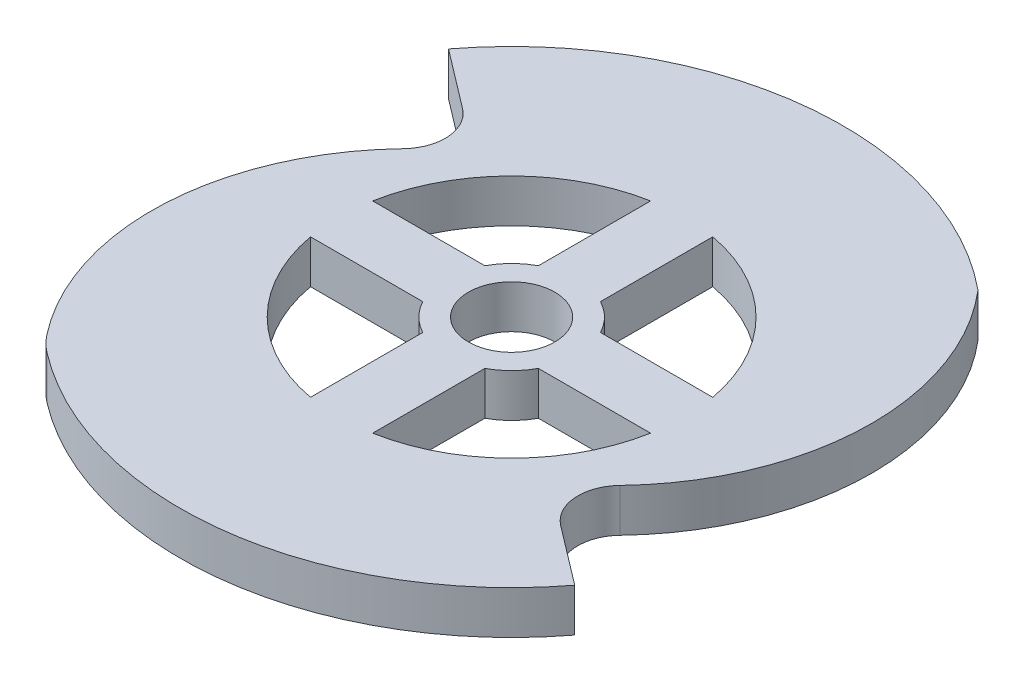
SolidWorks part; units mm, degrees
ref_plane "Front Plane" through (0, 0, 0) normal (0, 0, 1) x (1, 0, 0)
ref_plane "Top Plane" through (0, 0, 0) normal (0, 1, 0) x (1, 0, 0)
ref_plane "Right Plane" through (0, 0, 0) normal (1, 0, 0) x (0, 0, -1)
sketch "Sketch1" plane through (0, 0, 0) normal (0, 1, 0) x (1, 0, 0)
  line L0 (-61.0433, 46.4365) -> (-47.4391, 36.0875)
  line L5 (-61.0433, 46.4365) -> (61.0433, -46.4365) construction
  line L6 (-48.5581, -59.3696) -> (48.5581, 59.3696) construction
  line L7 (61.0433, -46.4365) -> (47.4391, -36.0875)
  line L17 (-7.1911, -13.1639) -> (-7.1911, -39.3483)
  line L26 (-7.1911, 39.3483) -> (-7.1911, 13.3811)
  line L28 (7.1911, 39.3483) -> (7.1911, 13.3811)
  line L29 (-7.1911, 39.3483) -> (7.1911, -39.3483) construction
  line L30 (-7.1911, -39.3483) -> (7.1911, 39.3483) construction
  line L31 (-39.3483, 7.1911) -> (-13.3811, 7.1911)
  line L33 (-39.3483, -7.1911) -> (-13.3811, -7.1911)
  line L35 (-39.3483, 7.1911) -> (39.3483, -7.1911) construction
  line L36 (-39.3483, -7.1911) -> (39.3483, 7.1911) construction
  line L38 (7.1911, -13.3811) -> (7.1911, -39.3483)
  line L39 (13.3811, 7.1911) -> (39.3483, 7.1911)
  line L42 (13.3811, -7.1911) -> (39.3483, -7.1911)
  arc A0 (-46.6235, -60.9006) -> (61.0433, -46.4365) centre (0, 0) ccw
  arc A1 (7.1911, -39.3483) -> (39.3483, -7.1911) centre (0, 0) ccw
  arc A2 (48.5581, 59.3696) -> (46.2784, -21.2046) centre (2.9877, 20.3396) cw
  arc A3 (-50.205, -57.3603) -> (-46.2784, 21.2046) centre (-2.9877, -20.3396) cw
  arc A4 (48.5581, 59.3696) -> (-61.0433, 46.4365) centre (0, 0) ccw
  arc A6 (-13.3811, -7.1911) -> (-7.1911, -13.3811) centre (0, 0) ccw
  arc A8 (13.3811, 7.1911) -> (7.1911, 13.3811) centre (0, 0) ccw
  arc A9 (-7.1911, 13.3811) -> (-13.3811, 7.1911) centre (0, 0) ccw
  arc A10 (-7.1911, 39.3483) -> (-39.3483, 7.1911) centre (0, 0) ccw
  arc A11 (39.3483, 7.1911) -> (7.1911, 39.3483) centre (0, 0) ccw
  arc A12 (-39.3483, -7.1911) -> (-7.1911, -39.3483) centre (0, 0) ccw
  circle A13 centre (0, 0) radius 10
  arc A14 (7.1911, -13.3811) -> (13.3811, -7.1911) centre (0, 0) ccw
  arc A15 (-46.6235, -60.9006) -> (-50.205, -57.3603) centre (-34.4659, -45.02) cw
  arc A16 (-47.4391, 36.0875) -> (-46.2784, 21.2046) centre (-53.4935, 28.1286) cw
  arc A17 (46.2784, -21.2046) -> (47.4391, -36.0875) centre (53.4935, -28.1286) ccw
  point P34 (37.6461, -28.6379)
  dimension "D1" = 20
  dimension "D2" = 10
  dimension "D3" = 10
extrude "Boss-Extrude4" add sketch "Sketch1" along normal blind 10 contours A2 A4 L0 A3 A0 L7 A13 A12 L33 A6 L17 A11 L39 A8 L28 A10 L26 A9 L31 L38 A14 L42 A1 region at (-8.7555, 0, -74.1986)
